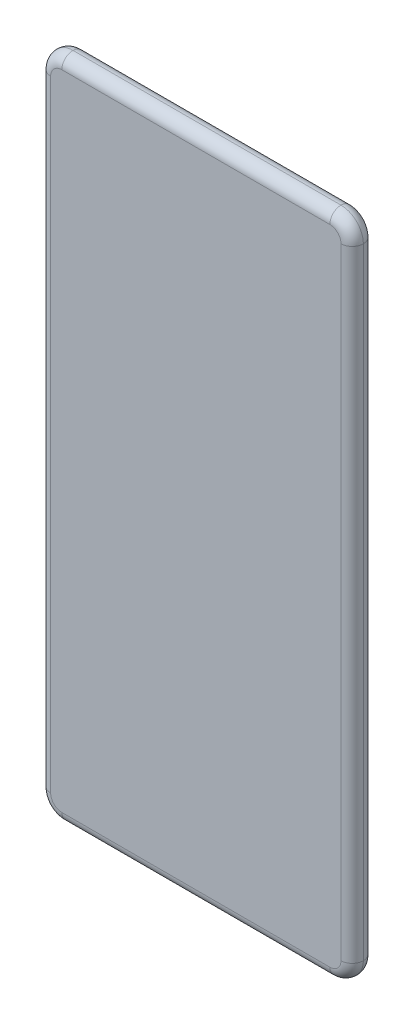
SolidWorks part; units mm, degrees
material "Natural Rubber"
ref_plane "Front Plane" through (0, 0, 0) normal (0, 0, 1) x (1, 0, 0)
ref_plane "Top Plane" through (0, 0, 0) normal (0, 1, 0) x (1, 0, 0)
ref_plane "Right Plane" through (0, 0, 0) normal (1, 0, 0) x (0, 0, -1)
sketch "Sketch1" plane through (0, 0, 0) normal (0, 0, 1) x (1, 0, 0)
  line L1 (-1300, -19) -> (-100, -19)
  line L2 (-1400, -119) -> (-1400, -2899)
  line L3 (-1300, -2999) -> (-100, -2999)
  line L4 (0, -119) -> (0, -2899)
  arc A0 (-1400, -2899) -> (-1300, -2999) centre (-1300, -2899) ccw
  arc A1 (-100, -2999) -> (0, -2899) centre (-100, -2899) ccw
  arc A2 (-100, -19) -> (0, -119) centre (-100, -119) cw
  arc A3 (-1300, -19) -> (-1400, -119) centre (-1300, -119) ccw
  point P6 (-1400, -2999)
  point P11 (0, -19)
  point P14 (-1400, -19)
  dimension "D3" = 100
  dimension "D1" = 1400
  dimension "D2" = 2980
extrude "Boss-Extrude1" add sketch "Sketch1" along normal blind 100
fillet "Fillet1" radius 50 16 edges at (-1370.7107, -2969.7107, 0) (-700, -2999, 0) (-29.2893, -2969.7107, 0) (0, -1509, 0) (-29.2893, -48.2893, 0) (-700, -19, 0) (-1370.7107, -48.2893, 0) (-1400, -1509, 0) (-1370.7107, -2969.7107, 100) (-700, -2999, 100) (-29.2893, -2969.7107, 100) (0, -1509, 100) (-29.2893, -48.2893, 100) (-700, -19, 100) (-1370.7107, -48.2893, 100) (-1400, -1509, 100)
